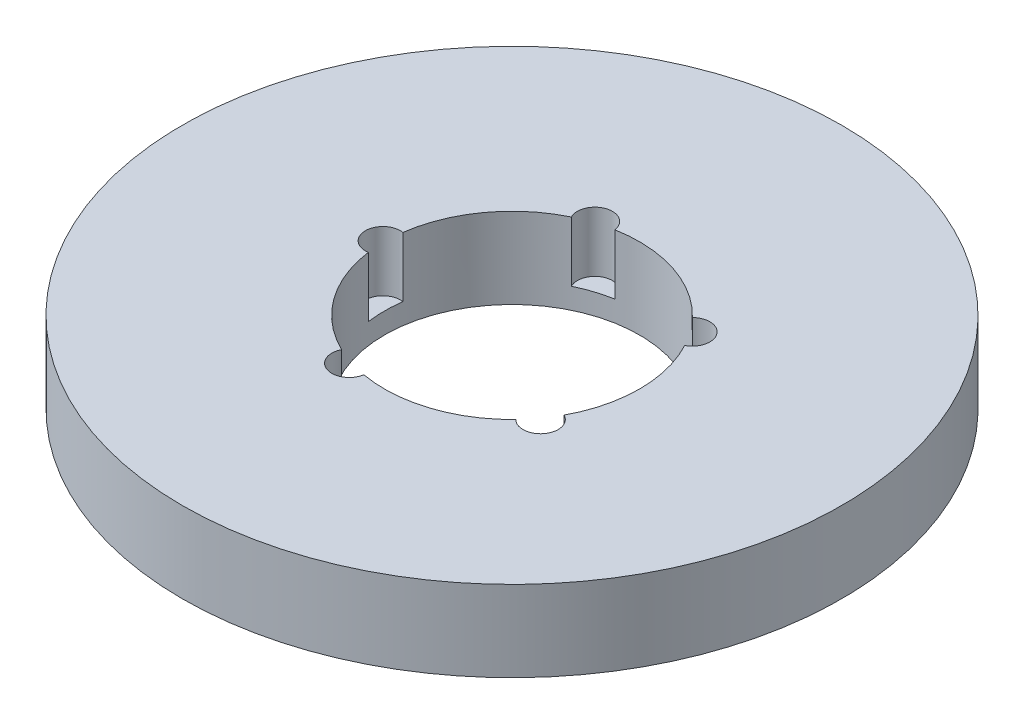
SolidWorks part; units mm, degrees
ref_plane "Front Plane" through (0, 0, 0) normal (0, 0, 1) x (1, 0, 0)
ref_plane "Top Plane" through (0, 0, 0) normal (0, 1, 0) x (1, 0, 0)
ref_plane "Right Plane" through (0, 0, 0) normal (1, 0, 0) x (0, 0, -1)
sketch "Sketch1" plane through (0, 0, 0) normal (0, 1, 0) x (1, 0, 0)
  circle A0 centre (0, 0) radius 77.5
  dimension "FLANGE_OD" = 155
extrude "Boss-Extrude1" add sketch "Sketch1" along normal blind 19
sketch "Sketch2" plane through (0, 0, 0) normal (0, 1, 0) x (1, 0, 0)
  circle A0 centre (0, 0) radius 30
  dimension "BORE_D" = 60
extrude "Cut-Extrude1" cut sketch "Sketch2" along normal through all
sketch "Sketch3" plane through (0, 19, 0) normal (0, 1, 0) x (1, 0, 0)
  circle A0 centre (0, 0) radius 30.3624 construction
  circle A1 centre (-30.3624, 0) radius 4.1193
  dimension "BOLT_D" = 8.2386
  dimension "BOLT_PCD" = 60.7247
extrude "Cut-Extrude2" cut sketch "Sketch3" against normal blind 14.1016
pattern_circular "CirPattern1" count 5 over 360 about axis through (0, 0, 0) along (0, 1, 0) of "Cut-Extrude2"
